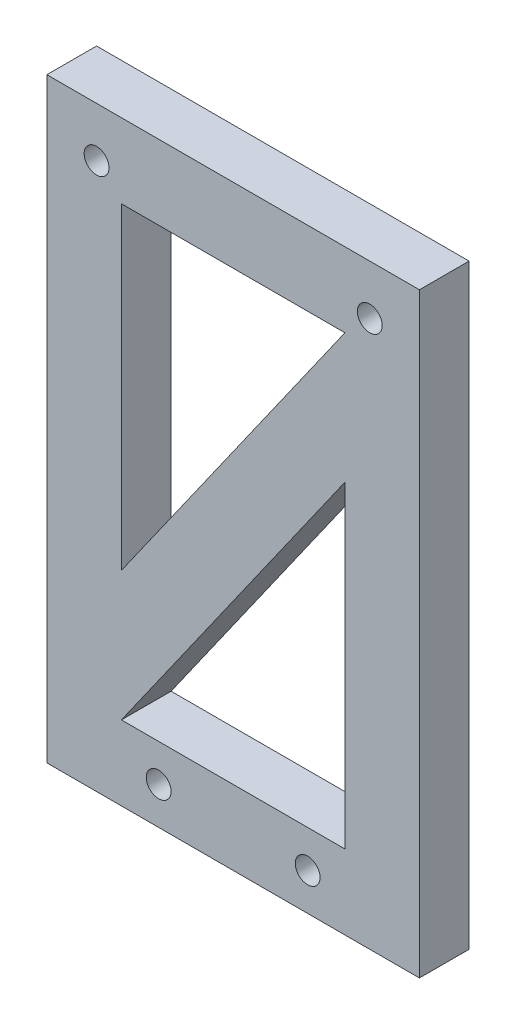
SolidWorks part; units mm, degrees
note: The reader was unsure of these and kept them because the rebuilt part matched: thickness of "Base-Flange1", "Sheet-Metal1", "Sheet-Metal2".
material "Acrylic (Medium-high impact)"
ref_plane "Front Plane" through (0, 0, 0) normal (0, 0, 1) x (1, 0, 0)
ref_plane "Top Plane" through (0, 0, 0) normal (0, 1, 0) x (1, 0, 0)
ref_plane "Right Plane" through (0, 0, 0) normal (1, 0, 0) x (0, 0, -1)
sketch "Sketch1" plane through (0, 0, 0) normal (0, 0, 1) x (1, 0, 0)
  line L1 (0, 0) -> (75, 0)
  line L2 (0, 0) -> (0, 120)
  line L3 (0, 120) -> (75, 120)
  line L4 (75, 0) -> (75, 120)
  dimension "D1" = 75
  dimension "D2" = 120
base flange "Base-Flange1" sketch "Sketch1" thickness 10 reverse thickness direction no parameters "D1"=0.7366
sketch "Sketch7" plane through (0, 0, 0) normal (0, 0, 1) x (1, 0, 0)
  line L0 (75, 120) -> (0, 120) construction
  line L1 (0, 0) -> (75, 0) construction
  line L2 (0, 120) -> (0, 0) construction
  line L3 (37.5, 120) -> (37.5, 0) construction
  line L4 (15, 105) -> (15, 41.062)
  line L5 (15, 41.062) -> (60, 105)
  line L6 (60, 105) -> (15, 105)
  line L7 (15, 15) -> (60, 15)
  line L8 (60, 15) -> (60, 78.938)
  line L9 (60, 78.938) -> (15, 15)
  line L10 (75, 0) -> (75, 120) construction
  circle A0 centre (10, 110) radius 2.5
  circle A1 centre (22.5, 7.5) radius 2.5
  circle A2 centre (52.5, 7.5) radius 2.5
  circle A3 centre (65, 110) radius 2.5
  dimension "D1" = 5
  dimension "D3" = 7.5
  dimension "D2" = 10
  dimension "D4" = 10
  dimension "D5" = 15
  dimension "D6" = 15
  dimension "D7" = 15
  dimension "D8" = 15
  dimension "D9" = 15
  dimension "D10" = 30
extrude "Cut-Extrude1" cut sketch "Sketch7" against normal blind 10 normal cut yes
sketch "Bend-Lines1" [suppressed] plane through (0, 0, 0) normal (0, 1, 0) x (1, 0, 0)
sketch "Bounding-Box1" [suppressed] plane through (0, 0, 0) normal (0, 1, 0) x (1, 0, 0)
sheet metal parameters "Sheet-Metal1" thickness 10 parameters "D1"=0.7366
flat pattern "Flat-Pattern1" [suppressed]
sketch "Bend-Lines2" plane through (0, 0, 0) normal (0, 1, 0) x (1, 0, 0)
sketch "Bounding-Box2" [suppressed] plane through (0, 0, 0) normal (0, 1, 0) x (1, 0, 0)
sheet metal parameters "Sheet-Metal2" thickness 10 parameters "D1"=0.7366
flat pattern "Flat-Pattern1"
sketch "Bend-Lines2" plane through (0, 0, 0) normal (0, 1, 0) x (1, 0, 0)
sketch3d "Bounding-Box2" [suppressed]
  line L0 (15, 127, 0) -> (15, 0, 0) construction
  line L1 (0, 127, 0) -> (0, 0, 0) construction
  line L2 (15, 127, 0) -> (0, 127, 0) construction
  line L3 (15, 0, 0) -> (0, 0, 0) construction
